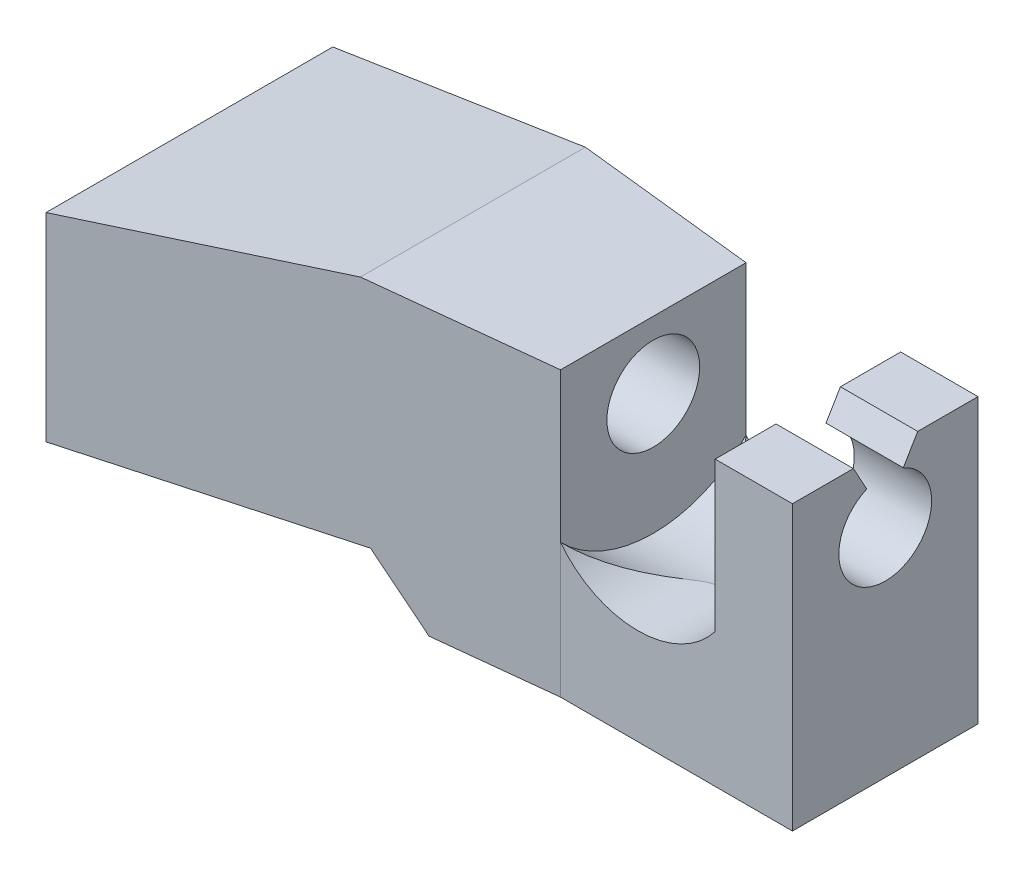
SolidWorks part; units mm, degrees
ref_plane "Front Plane" through (0, 0, 0) normal (0, 0, 1) x (1, 0, 0)
ref_plane "Top Plane" through (0, 0, 0) normal (0, 1, 0) x (1, 0, 0)
ref_plane "Right Plane" through (0, 0, 0) normal (1, 0, 0) x (0, 0, -1)
sketch "Sketch1" plane through (0, 0, 0) normal (0, 0, 1) x (1, 0, 0)
  line L0 (-25, 25) -> (25, 25)
  line L1 (25, 25) -> (25, -10)
  line L2 (25, -10) -> (45, -10)
  line L3 (45, -10) -> (130, 11.1135)
  line L4 (130, 11.1135) -> (165, 11.1135)
  line L5 (165, 11.1135) -> (165, -33.8865)
  line L6 (165, -33.8865) -> (130, -33.8865)
  line L7 (130, -33.8865) -> (45.0023, -45.0023)
  line L8 (45.0023, -45.0023) -> (-4.9977, -45.0023)
  line L9 (-4.9977, -45.0023) -> (-25, -25)
  line L10 (-25, -25) -> (-25, 25)
  line L11 (75, -2.5482) -> (75, -41.0792)
  line L12 (25, -10) -> (-4.9977, -45.0023)
  circle A1 centre (0, 0) radius 10
  point P16 (0, 25)
  point P19 (-25, 0)
  dimension "D1" = 20
  dimension "D2" = 50
  dimension "D3" = 50
  dimension "D4" = 35
  dimension "D5" = 20
  dimension "D6" = 135
  dimension "D7" = 50
  dimension "D8" = 190
  dimension "D9" = 100
  dimension "D10" = 87.583
  dimension "D11" = 35
  dimension "D12" = 45
extrude "Boss-Extrude2" add sketch "Sketch1" along normal mid plane 60 contours L12 L1 L0 L10 L9 A1 | L2 L12 L8 L7 L11 L3 | L3 L11 L7 L6 L5 L4 region at (0, 24.1397, 0) region at (42.4484, -27.4478, 0) region at (121.2251, -14.3996, 0)
sketch "Sketch3" plane through (0, 0, 0) normal (0, 0, 1) x (1, 0, 0)
sketch "Sketch4" plane through (0, 0, 0) normal (0, 0, 1) x (1, 0, 0)
  line L0 (75, -2.5482) -> (75, -41.0792) construction
  line L1 (25, -10) -> (45, -10) construction
  line L2 (45, -10) -> (130, 11.1135) construction
  line L3 (130, 11.1135) -> (165, 11.1135) construction
  line L4 (165, 11.1135) -> (165, -33.8865) construction
  line L5 (165, -33.8865) -> (130, -33.8865) construction
  line L6 (130, -33.8865) -> (45.0023, -45.0023) construction
  line L7 (45.0023, -45.0023) -> (-4.9977, -45.0023) construction
  line L8 (25, 25) -> (25, -10) construction
  line L9 (-25, 25) -> (25, 25) construction
  line L10 (-25, -25) -> (-25, 25) construction
  line L11 (-4.9977, -45.0023) -> (-25, -25) construction
  line L12 (25, -10) -> (-4.9977, -45.0023) construction
  line L13 (75, -2.5482) -> (75, -41.0792)
  line L14 (25, -10) -> (45, -10)
  line L15 (45, -10) -> (130, 11.1135)
  line L16 (130, 11.1135) -> (165, 11.1135)
  line L17 (165, 11.1135) -> (165, -33.8865)
  line L18 (165, -33.8865) -> (130, -33.8865)
  line L19 (130, -33.8865) -> (45.0023, -45.0023)
  line L20 (45.0023, -45.0023) -> (-4.9977, -45.0023)
  line L21 (25, 25) -> (25, -10)
  line L22 (-25, 25) -> (25, 25)
  line L23 (-25, -25) -> (-25, 25)
  line L24 (-4.9977, -45.0023) -> (-25, -25)
  line L25 (25, -10) -> (-4.9977, -45.0023)
  circle A1 centre (0, 0) radius 10
  circle A2 centre (0, 0) radius 10
  dimension "D1" = 0
extrude "Cut-Extrude1" cut sketch "Sketch4" against normal mid plane 30 contours L25 L21 L22 L23 L24 A2 region at (9.3479, -26.9413, 0)
chamfer "Chamfer1" distance 20 angle 45 2 edges at (25, -10, -22.5) (25, -10, 22.5)
sketch "Sketch5" plane through (0, 0, 0) normal (0, 1, 0) x (1, 0, 0)
  line L2 (165, 30) -> (165, -30)
  line L3 (165, -30) -> (55.0742, -30)
  line L4 (45, -30) -> (130, -30) construction
  line L5 (55.0742, -30) -> (165, -18)
  line L6 (165, 30) -> (55.0742, 30)
  line L7 (55.0742, 30) -> (165, 18)
  dimension "D2" = 6.23
extrude "Cut-Extrude2" cut sketch "Sketch5" against normal through all both and the other way through all contours L5 L3 L2 | L6 L7 L2 region at (128.3581, 0, 26) region at (128.3581, 0, -26)
sketch "Sketch6" plane through (165, 0, 0) normal (1, 0, 0) x (0, 0, -1)
  line L0 (-18, -33.8865) -> (18, -33.8865)
  line L1 (18, -33.8865) -> (18, -17.8865)
  line L2 (18, -33.8865) -> (18, 11.1135) construction
  line L3 (-18, -33.8865) -> (-18, -17.8865)
  line L4 (-18, -33.8865) -> (-18, 11.1135) construction
  line L6 (-18, 11.1135) -> (18, 11.1135) construction
  arc A1 (-18, -17.8865) -> (18, -17.8865) centre (0, 0) ccw
  circle A2 centre (0, -1.8865) radius 9
  dimension "D1" = 16
  dimension "D2" = 18
  dimension "D3" = 13
extrude "Boss-Extrude3" add sketch "Sketch6" along normal blind 45 contours A1 L1 L0 L3
sketch "Sketch7" plane through (165, 0, 0) normal (1, 0, 0) x (0, 0, -1)
extrude "Cut-Extrude3" cut sketch "Sketch6<3>" against normal blind 15 and the other way through all contours A2 region at (165, -1.8865, 0)
sketch "Sketch6<3>" plane through (165, 0, 0) normal (1, 0, 0) x (0, 0, -1) same geometry as "Sketch6"
sketch "Sketch8" plane through (0, -33.8865, 0) normal (0, -1, 0) x (1, 0, 0)
  line L0 (210, 18) -> (165, 18) construction
  line L1 (195, 18) -> (210, 18)
  line L2 (195, 18) -> (195, -18)
  line L3 (195, -18) -> (210, -18)
  line L4 (210, 18) -> (210, -18)
  dimension "D1" = 15
extrude "Boss-Extrude4" add sketch "Sketch8" against normal up to vertex (45 mm away) up to point (165, 11.1136, 18)
sketch "Sketch10" plane through (165, 0, 0) normal (1, 0, 0) x (0, 0, -1)
  line L3 (-18, 11.1135) -> (-18, -17.8865)
  line L4 (18, -17.8865) -> (18, 11.1135)
  line L5 (18, 11.1135) -> (-18, 11.1135)
  line L6 (-18, 11.1135) -> (-18, -17.8865)
  line L7 (18, -17.8865) -> (18, 11.1135)
  line L8 (18, 11.1135) -> (-18, 11.1135)
  circle A0 centre (0, -1.8865) radius 9 construction
  arc A1 (-18, -17.8865) -> (18, -17.8865) centre (0, 0) ccw
  arc A2 (-18, -17.8865) -> (18, -17.8865) centre (0, 0) ccw
  circle A3 centre (0, -1.8865) radius 9
  circle M5 centre (0, -1.8865) radius 9
  dimension "D1" = 0
extrude "Cut-Extrude4" cut sketch "Sketch10" along normal through all contours M5 region at (165, -1.8865, 0)
sketch "Sketch11" plane through (0, -33.8865, 0) normal (0, -1, 0) x (1, 0, 0)
  line L0 (130, 21.8208) -> (130, -21.8208)
  line L1 (130, -21.8208) -> (165, -18)
  line L2 (165, -18) -> (130, -21.8208) construction
  line L3 (210, -18) -> (165, -18) construction
  line L4 (165, -18) -> (210, -18)
  line L5 (210, -18) -> (210, 18)
  line L6 (210, 18) -> (165, 18)
  line L7 (210, 18) -> (165, 18) construction
  line L8 (165, 18) -> (130, 21.8208)
extrude "Boss-Extrude5" add sketch "Sketch11" along normal blind 10
chamfer "Chamfer2" distance 12 angle 45 1 edges at (130, -43.8865, 0)
sketch "Sketch13" plane through (0, 0, 18) normal (0, 0, 1) x (1, 0, 0)
  line L0 (165, -17.8865) -> (195, -17.8865)
  arc A0 (165, -17.8865) -> (195, -17.8865) centre (180, -6.2245) ccw
  dimension "D1" = 38
extrude "Cut-Extrude5" cut sketch "Sketch13" against normal blind 40
sketch "Sketch14" plane through (0, 0, 0) normal (0, 1, 0) x (1, 0, 0)
  line L1 (-25, -30) -> (75, -30)
  line L2 (-25, -30) -> (-25, 30)
  line L3 (-25, 30) -> (75, 30)
  line L4 (75, -30) -> (75, 30)
  dimension "D1" = 100
extrude "Cut-Extrude6" cut sketch "Sketch14" against normal through all both and the other way through all
sketch "Sketch16" plane through (75, 0, 0) normal (-1, 0, 0) x (0, 0, 1)
  circle A0 centre (0, -20.0323) radius 10
  dimension "D1" = 20
extrude "Cut-Extrude7" cut sketch "Sketch16" against normal blind 10 and the other way through all
sketch "Sketch17" plane through (210, 0, 0) normal (1, 0, 0) x (0, 0, -1)
  line L0 (-6.1828, 11.1135) -> (-3.5735, 6.3737)
  line L1 (6.3048, 11.1135) -> (3.5073, 6.402)
  line L4 (-18, 11.1135) -> (-18, -43.8865)
  line L5 (-18, -43.8865) -> (18, -43.8865)
  line L6 (18, -43.8865) -> (18, 11.1135)
  line L7 (18, 11.1135) -> (-18, 11.1135)
  line L9 (-18, -43.8865) -> (18, -43.8865)
  line L11 (6.3048, 11.1135) -> (-6.1828, 11.1135)
  circle A0 centre (0, -1.8865) radius 9 construction
  arc A1 (3.5073, 6.402) -> (-3.5735, 6.3737) centre (0, -1.8865) ccw
  point P10 (0, 0)
  point P11 (2.2133, 6.8371)
  point P12 (3.5073, 6.3737)
  dimension "D1" = 0
extrude "Cut-Extrude8" cut sketch "Sketch17" against normal up to surface (15 mm away) contours L1 A1 L0 L11 up to face at (195, -5.2588, 0)
